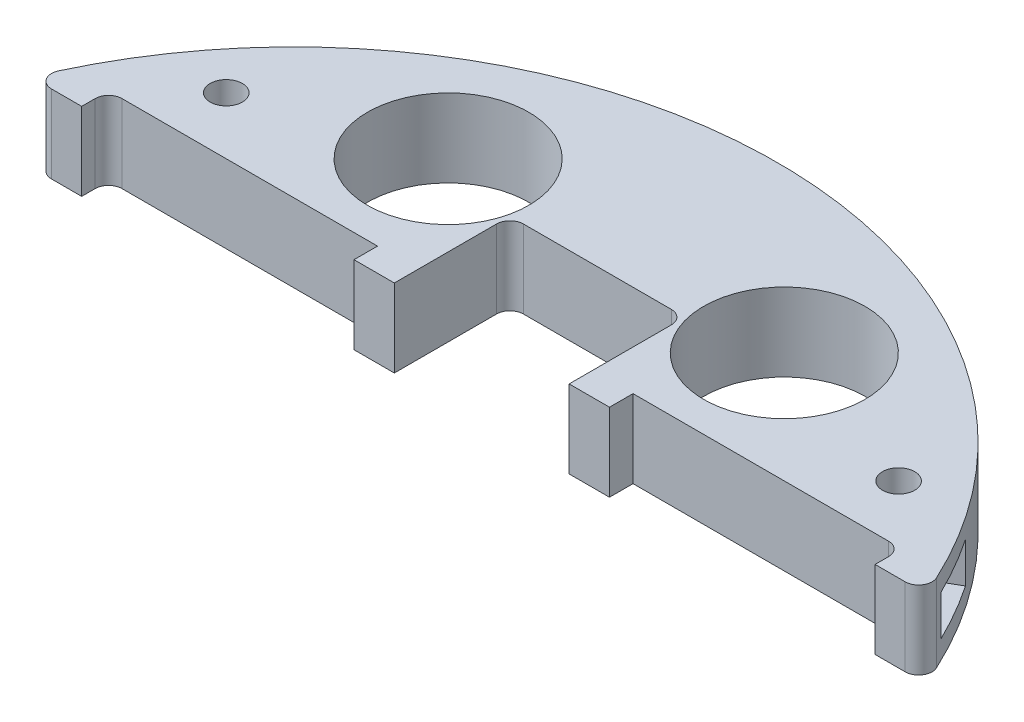
SolidWorks part; units mm, degrees
material "ABS"
ref_plane "Front Plane" through (0, 0, 0) normal (0, 0, 1) x (1, 0, 0)
ref_plane "Top Plane" through (0, 0, 0) normal (0, 1, 0) x (1, 0, 0)
ref_plane "Right Plane" through (0, 0, 0) normal (1, 0, 0) x (0, 0, -1)
sketch "Sketch1" plane through (0, 0, 0) normal (0, 1, 0) x (1, 0, 0)
  line L0 (0, -85) -> (-32.2211, -64.3879) construction
  line L1 (0, -85) -> (0, 0) construction
  arc A0 (36.2245, -62.2237) -> (-36.2245, -62.2237) centre (0, 0) ccw
  arc A1 (29.8119, -61.0352) -> (-29.8119, -61.0352) centre (0, -85) ccw
  arc A2 (36.2245, -62.2237) -> (29.8119, -61.0352) centre (33.7089, -57.9026) cw
  arc A3 (-29.8119, -61.0352) -> (-36.2245, -62.2237) centre (-33.7089, -57.9026) cw
  dimension "D1" = 144
  dimension "D2" = 76.5
  dimension "D4" = 5
  dimension "D3" = 85
extrude "Boss-Extrude1" add sketch "Sketch1" along normal mid plane 11.6
sketch "solenoid placement" plane through (0, 5.8, 0) normal (0, 1, 0) x (1, 0, 0)
  line L0 (0, 0) -> (0, -36) construction
  line L5 (-19, -36) -> (19, -36)
  line L7 (19, -36) -> (19, 28)
  line L9 (19, 28) -> (-19, 28)
  line L11 (-19, 28) -> (-19, -36)
  circle A1 centre (0, 0) radius 72 construction
  arc A2 (36.2245, -62.2237) -> (-36.2245, -62.2237) centre (0, 0) ccw construction
  dimension "D1" = 36
  dimension "D2" = 64
  dimension "D3" = 38
extrude "Cut-Extrude1" cut sketch "solenoid placement" against normal through all
sketch "Sketch4" plane through (0, 5.8, 0) normal (0, 1, 0) x (1, 0, 0)
  line L1 (-13, 28) -> (13, 28)
  line L2 (-13, 28) -> (-13, 43.2)
  line L4 (13, 28) -> (13, 43.2)
  line L5 (11, 45.2) -> (-11, 45.2)
  line L6 (19, 28) -> (-19, 28) construction
  arc A0 (11, 45.2) -> (13, 43.2) centre (11, 43.2) cw
  arc A1 (-11, 45.2) -> (-13, 43.2) centre (-11, 43.2) ccw
  point P6 (0, 28)
  dimension "D1" = 2
  dimension "D2" = 26
  dimension "D3" = 17.2
extrude "Cut-Extrude4" cut sketch "Sketch4" against normal through all
sketch "Sketch5" plane through (0, 5.8, 0) normal (0, 1, 0) x (1, 0, 0)
  line L0 (0, 0) -> (0, 72) construction
  arc A0 (36.2245, -62.2237) -> (-36.2245, -62.2237) centre (0, 0) ccw construction
  circle A1 centre (25, 48) radius 12
  circle A3 centre (-25, 48) radius 12
  dimension "D3" = 24
  dimension "D1" = 25
  dimension "D2" = 48
extrude "Cut-Extrude5" cut sketch "Sketch5" against normal through all
sketch "Sketch6" plane through (0, 5.8, 0) normal (0, 1, 0) x (1, 0, 0)
  line L0 (0, 0) -> (0, 72) construction
  arc A0 (36.2245, -62.2237) -> (-36.2245, -62.2237) centre (0, 0) ccw construction
  circle A1 centre (50, 40) radius 2.4
  circle A6 centre (-50, 40) radius 2.4
  dimension "D3" = 4.8
  dimension "D1" = 50
  dimension "D2" = 40
extrude "Cut-Extrude6" cut sketch "Sketch6" against normal through all
sketch "Sketch3" plane through (0, 5.8, 0) normal (0, 1, 0) x (1, 0, 0)
  line L0 (-19, 28) -> (19, 28)
  line L1 (-72, -31.5) -> (72, -31.5) construction
  line L2 (-72, -31.5) -> (-72, 27.5)
  line L3 (-59, 31.5) -> (-19, 31.5)
  line L4 (72, -31.5) -> (72, 27.5)
  line L5 (0, -31.5) -> (0, 31.5) construction
  line L6 (72, 27.5) -> (59, 27.5)
  line L7 (19, 28) -> (19, 31.5)
  line L8 (-19, 28) -> (-19, 31.5)
  line L9 (19, 31.5) -> (59, 31.5)
  line L10 (-72, -31.5) -> (-72, -101.6464)
  line L11 (72, -31.5) -> (72, -101.6464)
  line L12 (72, -101.6464) -> (-72, -101.6464)
  line L13 (59, 27.5) -> (59, 31.5)
  line L14 (-59, 27.5) -> (-59, 31.5)
  line L15 (-72, 27.5) -> (-59, 27.5)
  arc A0 (36.2245, -62.2237) -> (-36.2245, -62.2237) centre (0, 0) ccw construction
  point P0 (0, 0)
  dimension "D2" = 13
  dimension "D1" = 63
  dimension "D3" = 4
extrude "Cut-Extrude3" cut sketch "Sketch3" against normal through all
sketch "Sketch7" plane through (0, 0, 0) normal (0, 1, 0) x (1, 0, 0)
  line L0 (0, 0) -> (62.3538, 36) construction
  line L1 (0, 0) -> (-62.3538, 36) construction
  line L2 (0, 0) -> (0, 72) construction
  arc A0 (0, 72) -> (62.3538, 36) centre (0, 0) cw construction
  arc A1 (0, 72) -> (-62.3538, 36) centre (0, 0) ccw construction
  arc A2 (66.5413, 27.5) -> (-66.5413, 27.5) centre (0, 0) ccw construction
  point P6 (71.0061, 77.4865)
  point P7 (-73.326, 73.326)
  point P10 (-57.5324, 44.9335)
  point P11 (0, 0)
  dimension "D1" = 120
fillet "Fillet1" radius 2 4 edges at (-66.5413, 0, -27.5) (-59, 0, -31.5) (59, 0, -31.5) (66.5413, 0, -27.5)
sketch "Sketch8" plane through (0, 0, 0) normal (0, 1, 0) x (1, 0, 0)
  line L0 (5, 71.8262) -> (5, 68.9262)
  line L1 (0, 0) -> (64.7033, 31.583) construction
  line L2 (64.7033, 31.583) -> (59.7033, 40.2432) construction
  line L3 (64.7033, 31.583) -> (62.1918, 30.133)
  line L4 (62.1918, 30.133) -> (57.1918, 38.7932)
  line L5 (59.7033, 40.2432) -> (57.1918, 38.7932)
  line L6 (0, 0) -> (59.7033, 40.2432) construction
  line L7 (5, 68.9262) -> (-5, 68.9262)
  line L8 (-5, 71.8262) -> (-5, 68.9262)
  line L9 (5, 71.8262) -> (-5, 71.8262) construction
  line L10 (-59.7033, 40.2432) -> (-57.1918, 38.7932)
  line L11 (-57.1918, 38.7932) -> (-62.1918, 30.133)
  line L12 (-64.7033, 31.583) -> (-62.1918, 30.133)
  line L13 (-59.7033, 40.2432) -> (-64.7033, 31.583) construction
  arc A0 (59.7033, 40.2432) -> (64.7033, 31.583) centre (0, 0) cw
  arc A2 (-5, 71.8262) -> (5, 71.8262) centre (0, 0) cw
  arc A3 (-64.7033, 31.583) -> (-59.7033, 40.2432) centre (0, 0) cw
  point P4 (62.3538, 36)
  point P9 (-61.2214, 37.2956)
  point P10 (-62.3538, 36)
  point P18 (0, 0)
  dimension "D1" = 10
  dimension "D2" = 2.9
extrude "Cut-Extrude7" cut sketch "Sketch8" against normal mid plane 6
equation "\"smallPulleyTeeth\"= 15"
equation "\"largePulleyTeeth\"= 30"
equation "\"eighthThick\"= 2.9mm"
equation "\"sixteenthThick\" = 1.7mm"
equation "\"quarterThick\"=6.0mm"
equation "\"OD\" = 146mm"
equation "\"puckAngle\" = 60.5deg"
equation "\"puckDiam\" = 76.5mm"
equation "\"D2@Sketch1\"=\"puckDiam\""
equation "\"D1@Boss-Extrude1\"=\"eighthThick\"*4"
equation "\"axlePress\" = 5.9mm"
equation "\"press\" = 0.2mm"
equation "\"wheelClear\" = 0.3mm"
equation "\"10-32clear\" = 4.8mm"
equation "\"6-32clear\" = 3.3mm"
equation "\"8-32clear\" = 4.0mm"
equation "\"wheelHeight\" = 22mm"
equation "\"wheelWell\" = 65mm"
equation "\"puckDist\" = 85mm"
equation "\"scoopFillet\" = 5mm"
equation "\"4-40clear\" = 3.0mm"
equation "\"D3@Sketch1\"=\"puckDist\""
equation "\"D4@Sketch1\"=\"scoopFillet\""
equation "\"D3@Sketch6\"=\"10-32clear\""
equation "\"D2@Sketch8\"=\"eighthThick\""
